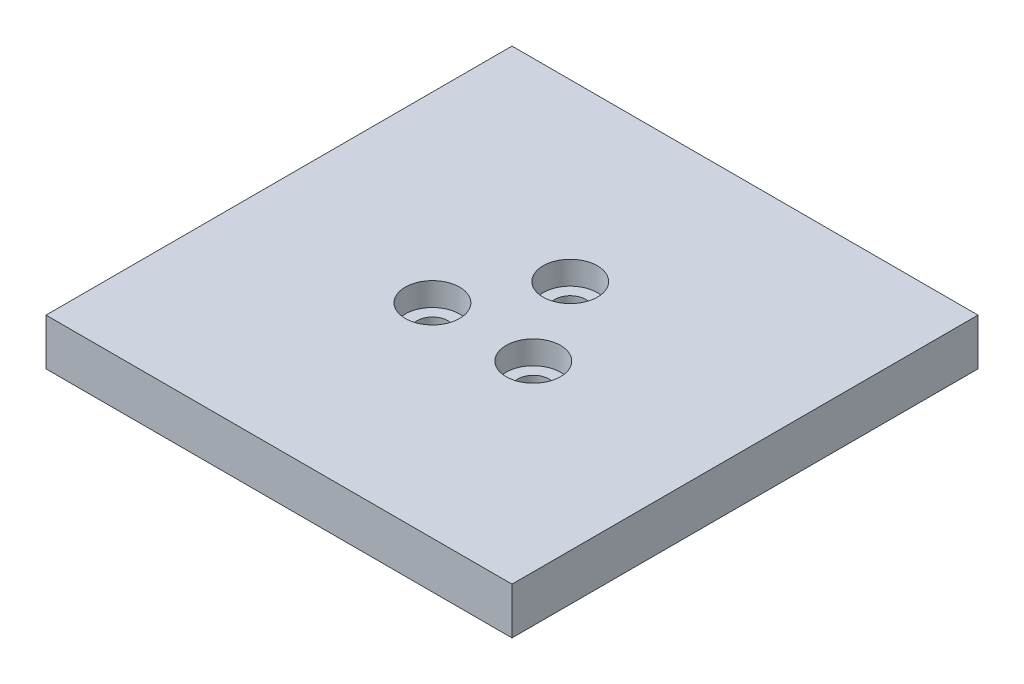
SolidWorks part; units mm, degrees
ref_plane "Front Plane" through (0, 0, 0) normal (0, 0, 1) x (1, 0, 0)
ref_plane "Top Plane" through (0, 0, 0) normal (0, 1, 0) x (1, 0, 0)
ref_plane "Right Plane" through (0, 0, 0) normal (1, 0, 0) x (0, 0, -1)
sketch "Sketch1" plane through (0, 0, 0) normal (0, 1, 0) x (1, 0, 0)
  line L1 (-30, -30) -> (30, -30)
  line L2 (-30, -30) -> (-30, 30)
  line L3 (-30, 30) -> (30, 30)
  line L4 (30, -30) -> (30, 30)
  line L5 (-30, -30) -> (30, 30) construction
  line L6 (-30, 30) -> (30, -30) construction
  circle A0 centre (0, 0) radius 7.5 construction
  circle A1 centre (0, 7.5) radius 2
  circle A2 centre (6.4952, -3.75) radius 2
  circle A3 centre (-6.4952, -3.75) radius 2
  circle A4 centre (0, 7.5) radius 3.5
  circle A5 centre (6.4952, -3.75) radius 3.5
  circle A6 centre (-6.4952, -3.75) radius 3.5
  point P0 (0, 0)
  point P17 (0, 0)
  point P22 (0, 0)
  dimension "D1" = 4
  dimension "D5" = 15
  dimension "D6" = 7
  dimension "D3" = 60
  dimension "D4" = 60
  dimension "D2" = 3
  dimension "D7" = 3
extrude "Boss-Extrude2" add sketch "Sketch1" along normal blind 6 contours L1 L4 L3 L2
extrude "Cut-Extrude1" cut sketch "Sketch1<4>" along normal through all contours A3 | A1 | A2
sketch "Sketch1<4>" plane through (0, 0, 0) normal (0, 1, 0) x (1, 0, 0) same geometry as "Sketch1"
extrude "Cut-Extrude2" cut sketch "Sketch1<5>" against normal blind 3 from surface contours A6 | A5 | A4 starting at face at (-6.4952, 6, 5.75)
sketch "Sketch1<5>" plane through (0, 0, 0) normal (0, 1, 0) x (1, 0, 0) same geometry as "Sketch1"
